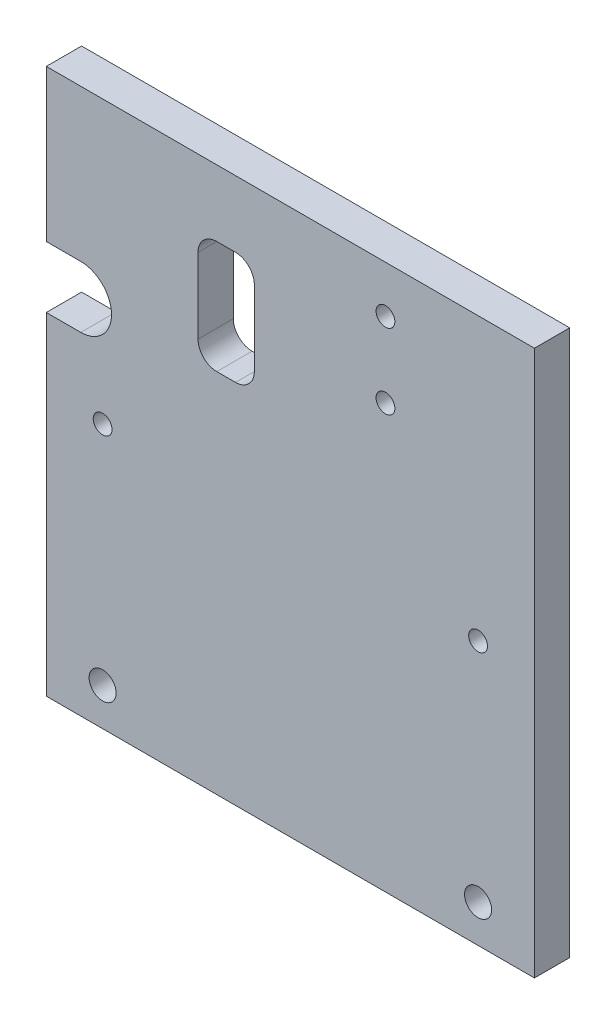
SolidWorks part; units mm, degrees
ref_plane "Front Plane" through (0, 0, 0) normal (0, 0, 1) x (1, 0, 0)
ref_plane "Top Plane" through (0, 0, 0) normal (0, 1, 0) x (1, 0, 0)
ref_plane "Right Plane" through (0, 0, 0) normal (1, 0, 0) x (0, 0, -1)
sketch "Sketch1" plane through (0, 0, 0) normal (0, 0, 1) x (1, 0, 0)
  line L5 (0, 0) -> (100, 0) construction
  line L6 (0, 0) -> (0, 60.26) construction
  line L7 (0, 60.26) -> (100, 60.26) construction
  line L8 (100, 0) -> (100, 60.26) construction
  line L9 (0, 0) -> (100, 60.26) construction
  line L10 (0, 60.26) -> (100, 0) construction
  line L11 (-15, -10) -> (115, -10)
  line L12 (-15, -10) -> (-15, 135.26)
  line L13 (-15, 135.26) -> (115, 135.26)
  line L14 (115, -10) -> (115, 135.26)
  line L15 (-15, -10) -> (115, 135.26) construction
  line L16 (-15, 135.26) -> (115, -10) construction
  circle A0 centre (0, 0) radius 3.6
  circle A1 centre (0, 60.26) radius 2.5
  circle A2 centre (100, 60.26) radius 2.5
  circle A3 centre (100, 0) radius 3.6
  point P6 (50, 30.13)
  point P16 (50, 62.63)
  dimension "D1" = 7.2
  dimension "D3" = 5
  dimension "D2" = 60.26
  dimension "D4" = 100
  dimension "D5" = 15
  dimension "D6" = 15
  dimension "D7" = 10
  dimension "D8" = 75
extrude "Boss-Extrude1" add sketch "Sketch1" along normal blind 9.4
sketch "Sketch2" plane through (0, 0, 9.4) normal (0, 0, 1) x (1, 0, 0)
  circle A2 centre (75.33, 122.7664) radius 2.5
  circle A3 centre (75.33, 102.7664) radius 2.5
  dimension "D1" = 5
  dimension "D2" = 5
extrude "Cut-Extrude1" cut sketch "Sketch2" against normal through all
sketch "Sketch3" plane through (0, 0, 0) normal (0, 0, -1) x (-1, 0, 0)
  line L1 (-35.4075, 117.5704) -> (-30.4075, 117.5704)
  line L2 (-40.4075, 112.5704) -> (-40.4075, 92.5704)
  line L3 (-35.4075, 87.5704) -> (-30.4075, 87.5704)
  line L4 (-25.4075, 112.5704) -> (-25.4075, 92.5704)
  line L5 (-40.4075, 117.5704) -> (-25.4075, 87.5704) construction
  line L6 (-40.4075, 87.5704) -> (-25.4075, 117.5704) construction
  arc A0 (-25.4075, 92.5704) -> (-30.4075, 87.5704) centre (-30.4075, 92.5704) cw
  arc A1 (-35.4075, 87.5704) -> (-40.4075, 92.5704) centre (-35.4075, 92.5704) cw
  arc A2 (-40.4075, 112.5704) -> (-35.4075, 117.5704) centre (-35.4075, 112.5704) cw
  arc A3 (-30.4075, 117.5704) -> (-25.4075, 112.5704) centre (-30.4075, 112.5704) cw
  point P4 (-32.9075, 102.5704)
  dimension "D1" = 5
  dimension "D2" = 30
  dimension "D3" = 15
extrude "Cut-Extrude2" cut sketch "Sketch3" against normal through all
sketch "Sketch4" plane through (0, 0, 9.4) normal (0, 0, 1) x (1, 0, 0)
  line L1 (-15, 135.26) -> (-15, -10) construction
  line L4 (-15, 78.5) -> (-15, 94.86)
  line L5 (-15, 94.86) -> (-5.81, 94.86)
  line L6 (-15, 78.5) -> (-5.81, 78.5)
  line L8 (115, 135.26) -> (-15, 135.26) construction
  arc A2 (-5.81, 94.86) -> (-5.81, 78.5) centre (-5.81, 86.68) cw
  dimension "D1" = 9.19
  dimension "D2" = 16.36
  dimension "D3" = 40.4
extrude "Cut-Extrude3" cut sketch "Sketch4" against normal through all
